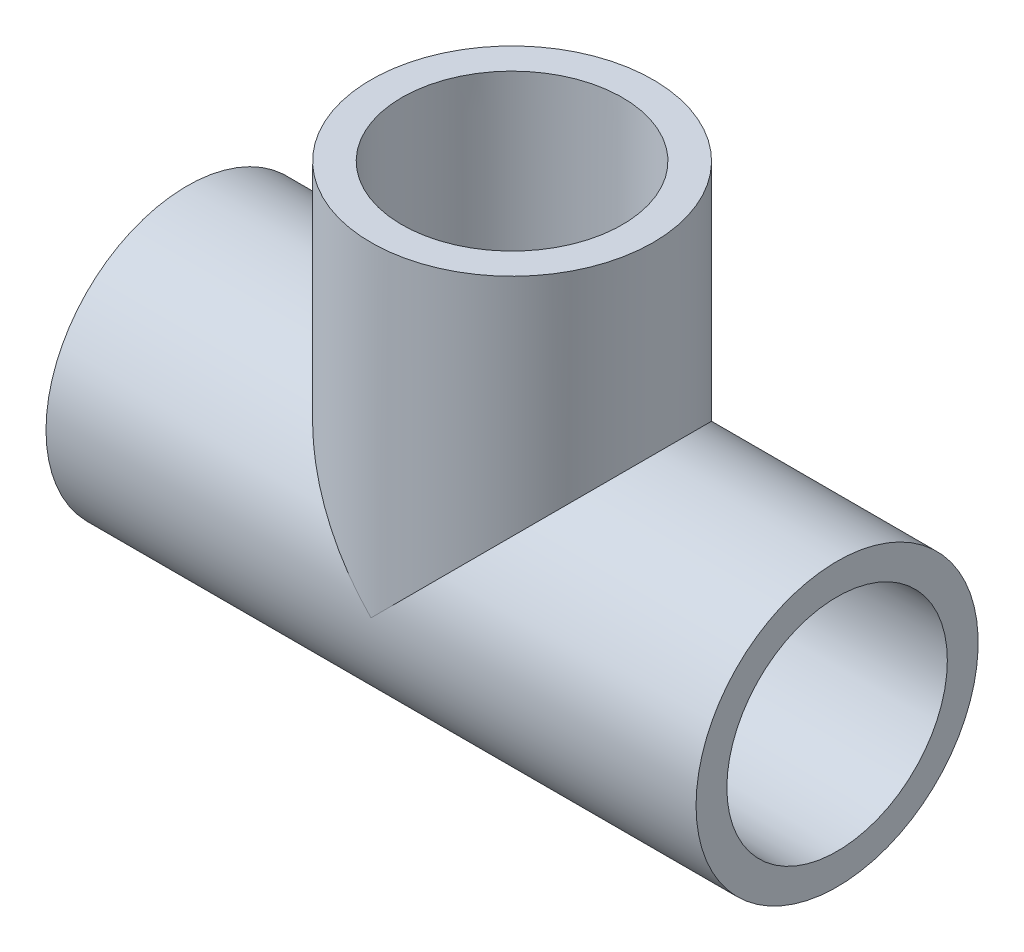
SolidWorks part; units mm, degrees
ref_plane "Front Plane" through (0, 0, 0) normal (0, 0, 1) x (1, 0, 0)
ref_plane "Top Plane" through (0, 0, 0) normal (0, 1, 0) x (1, 0, 0)
ref_plane "Right Plane" through (0, 0, 0) normal (1, 0, 0) x (0, 0, -1)
sketch "Sketch0" plane through (0, 0, 0) normal (0, 0, 1) x (1, 0, 0)
  line L0 (-31.75, 0) -> (0, 0) construction
  line L1 (0, 0) -> (0, 31.75) construction
  line L2 (-12.7, 0) -> (0, 0) construction
  line L3 (0, 0) -> (0, 12.7) construction
  line L4 (-31.75, 13.7795) -> (-31.75, -13.7795) construction
  line L5 (-12.7, 10.6172) -> (-31.75, 10.7696) construction
  line L6 (-12.7, 10.6172) -> (-12.7, -10.6172) construction
  line L7 (-12.7, -10.6172) -> (-31.75, -10.7696) construction
  line L8 (-31.75, 10.7696) -> (-31.75, -10.7696) construction
  line L9 (-13.7795, 31.75) -> (13.7795, 31.75) construction
  line L10 (-10.7696, 31.75) -> (10.7696, 31.75) construction
  line L11 (10.7696, 31.75) -> (10.6172, 12.7) construction
  line L12 (10.6172, 12.7) -> (-10.6172, 12.7) construction
  line L13 (-10.6172, 12.7) -> (-10.7696, 31.75) construction
  line L14 (-12.7, 7.8994) -> (-12.7, -7.8994) construction
  line L15 (-31.75, 0) -> (-12.7, 0) construction
  line L16 (0, 31.75) -> (0, 12.7) construction
  line L17 (0, 0) -> (12.7, 0) construction
  line L18 (-7.8994, 12.7) -> (7.8994, 12.7) construction
  line L19 (12.7, 0) -> (31.75, 0) construction
  dimension "H" = 31.75
  dimension "G" = 12.7
  dimension "M" = 27.559
  dimension "OD A" = 21.5392
  dimension "OD B" = 21.2344
  dimension "ID" = 15.7988
  dimension "H3" = 31.75
sketch "Sketch1" plane through (0, 0, 0) normal (0, 0, 1) x (1, 0, 0)
  line L0 (-31.75, 0) -> (0, 0) construction
  line L1 (-31.75, 0) -> (0, 0) construction
  line L2 (0, 0) -> (0, -13.7795) construction
  line L3 (-31.75, -13.7795) -> (-12.7, -13.7795)
  line L4 (-31.75, -13.7795) -> (-31.75, -10.7696)
  line L5 (-31.75, -10.7696) -> (-12.7, -10.6172)
  line L6 (-12.7, -13.7795) -> (-12.7, -10.6172)
  line L7 (-12.7, -13.7795) -> (0, -13.7795) construction
  line L8 (31.75, -10.7696) -> (12.7, -10.6172)
  line L9 (31.75, -13.7795) -> (31.75, -10.7696)
  line L10 (12.7, -13.7795) -> (12.7, -10.6172)
  line L11 (31.75, -13.7795) -> (12.7, -13.7795)
revolve "Revolve1" add sketch "Sketch1" angle 360 about L1
sketch "Sketch2" plane through (0, 0, 0) normal (0, 0, 1) x (1, 0, 0)
  line L0 (10.7696, 31.75) -> (10.6172, 12.7)
  line L1 (10.6172, 12.7) -> (13.7795, 12.7)
  line L2 (13.7795, 12.7) -> (13.7795, 31.75)
  line L3 (13.7795, 31.75) -> (10.7696, 31.75)
  line L4 (0, 0) -> (0, 31.75) construction
  line L5 (0, 0) -> (0, 31.75) construction
revolve "Revolve2" add sketch "Sketch2" angle 360 about L5
sketch "Sketch3" plane through (-12.7, 0, 0) normal (1, 0, 0) x (0, 0, -1)
  circle A0 centre (0, 0) radius 7.8994
  circle A1 centre (0, 0) radius 13.7795
sketch "Sketch4" plane through (-12.7, 0, 0) normal (1, 0, 0) x (0, 0, -1)
  circle A0 centre (0, 0) radius 13.7795 construction
  circle A1 centre (0, 0) radius 13.7795
extrude "Boss-Extrude1" add sketch "Sketch4" along normal up to vertex (25.4 mm away) up to point (12.7, 0, 0)
sketch "Sketch5" plane through (0, 12.7, 0) normal (0, -1, 0) x (1, 0, 0)
  circle A0 centre (0, 0) radius 13.7795 construction
  circle A1 centre (0, 0) radius 13.7795
extrude "Boss-Extrude2" add sketch "Sketch5" along normal up to vertex (12.7 mm away) up to point (0, 0, 0)
sketch "Sketch6" plane through (0, 0, 0) normal (0, 0, 1) x (1, 0, 0)
  line L0 (-31.75, -10.7696) -> (-12.7, -10.6172)
  line L1 (-12.7, -10.6172) -> (-12.7, -7.8994)
  line L2 (-12.7, -7.8994) -> (12.7, -7.8994)
  line L3 (12.7, -10.6172) -> (12.7, 9.1728) construction
  line L4 (0, -7.8994) -> (0, 0) construction
  line L5 (12.7, -10.6172) -> (12.7, -7.8994)
  line L6 (31.75, -10.7696) -> (31.75, 10.7696) construction
  line L7 (31.75, -13.7795) -> (31.75, 13.7795) construction
  line L8 (31.75, -10.7696) -> (31.75, 0)
  line L9 (31.75, 0) -> (-31.75, 0)
  line L10 (-31.75, 0) -> (-31.75, -10.7696)
  line L11 (31.75, -10.7696) -> (12.7, -10.6172)
revolve "Cut-Revolve1" cut sketch "Sketch6" angle 360 about L9
sketch "Sketch7" plane through (0, 0, 0) normal (0, 0, 1) x (1, 0, 0)
  line L0 (10.7696, 31.75) -> (10.6172, 12.7)
  line L1 (10.6172, 12.7) -> (7.8994, 12.7)
  line L2 (7.8994, 12.7) -> (7.8994, 0)
  line L3 (0, 0) -> (12.7, 0) construction
  line L4 (7.8994, 0) -> (0, 0)
  line L5 (0, 0) -> (0, 31.75)
  line L6 (-13.7795, 31.75) -> (13.7795, 31.75) construction
  line L7 (0, 31.75) -> (10.7696, 31.75)
revolve "Cut-Revolve2" cut sketch "Sketch7" angle 360 about L5
